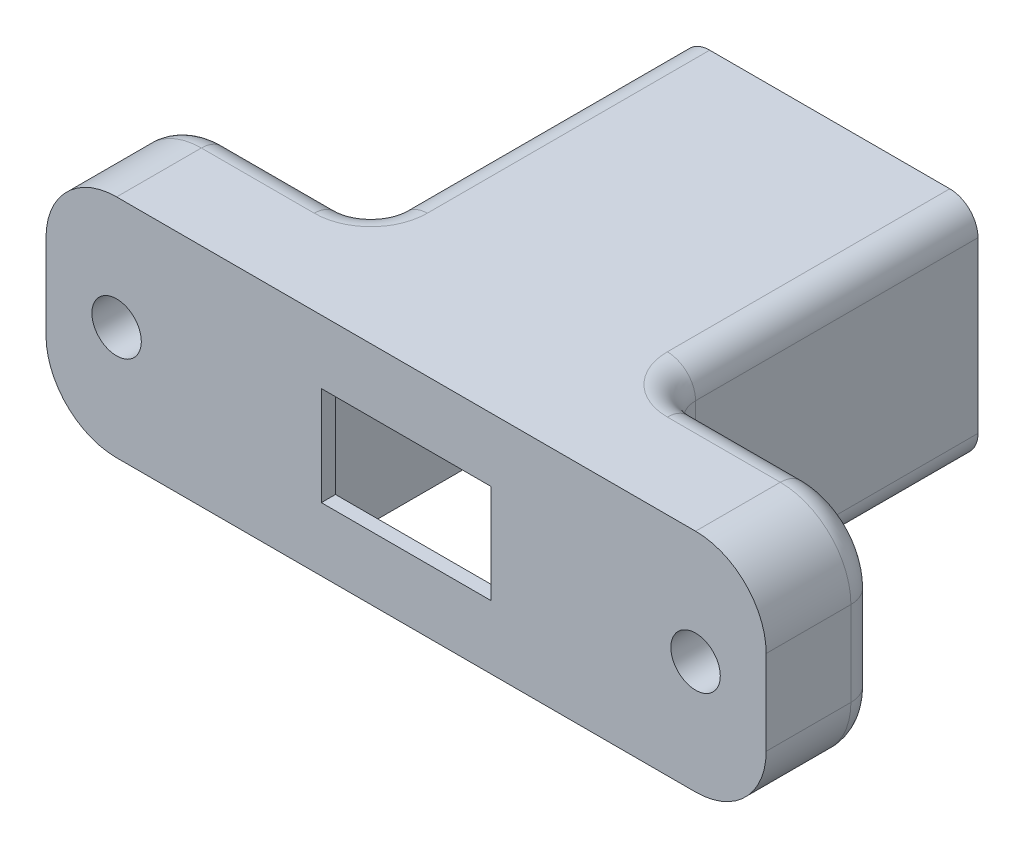
SolidWorks part; units mm, degrees
ref_plane "Front Plane" through (0, 0, 0) normal (0, 0, 1) x (1, 0, 0)
ref_plane "Top Plane" through (0, 0, 0) normal (0, 1, 0) x (1, 0, 0)
ref_plane "Right Plane" through (0, 0, 0) normal (1, 0, 0) x (0, 0, -1)
sketch "Sketch1" plane through (0, 0, 0) normal (0, 0, 1) x (1, 0, 0)
  line L1 (0, 0) -> (15, 0)
  line L2 (0, 0) -> (0, 10)
  line L3 (0, 10) -> (15, 10)
  line L4 (15, 0) -> (15, 10)
  line L5 (-3, 13) -> (18, 13)
  line L6 (-3, 13) -> (-3, -3)
  line L7 (-3, -3) -> (18, -3)
  line L8 (18, 13) -> (18, -3)
  line L9 (1.5, 8.5) -> (13.5, 8.5)
  line L10 (1.5, 8.5) -> (1.5, 1.5)
  line L11 (1.5, 1.5) -> (13.5, 1.5)
  line L12 (13.5, 8.5) -> (13.5, 1.5)
  line L13 (-13, 13) -> (28, 13)
  line L14 (-18, 8) -> (-18, 2)
  line L15 (-13, -3) -> (28, -3)
  line L16 (33, 8) -> (33, 2)
  line L17 (0, 0) -> (15, 0)
  line L18 (0, 0) -> (0, -3)
  line L19 (0, -3) -> (15, -3)
  line L20 (15, 0) -> (15, -3)
  line L21 (-9.7668, 5) -> (-11.3834, 7.8)
  line L22 (-11.3834, 7.8) -> (-14.6166, 7.8)
  line L23 (-14.6166, 7.8) -> (-16.2332, 5)
  line L24 (-16.2332, 5) -> (-14.6166, 2.2)
  line L25 (-14.6166, 2.2) -> (-11.3834, 2.2)
  line L26 (-11.3834, 2.2) -> (-9.7668, 5)
  line L27 (24.7668, 5) -> (26.3834, 2.2)
  line L28 (26.3834, 2.2) -> (29.6166, 2.2)
  line L29 (29.6166, 2.2) -> (31.2332, 5)
  line L30 (31.2332, 5) -> (29.6166, 7.8)
  line L31 (29.6166, 7.8) -> (26.3834, 7.8)
  line L32 (26.3834, 7.8) -> (24.7668, 5)
  circle A0 centre (-13, 5) radius 1.75
  circle A1 centre (28, 5) radius 1.75
  arc A2 (28, -3) -> (33, 2) centre (28, 2) ccw
  arc A3 (28, 13) -> (33, 8) centre (28, 8) cw
  arc A4 (-18, 2) -> (-13, -3) centre (-13, 2) ccw
  arc A5 (-13, 13) -> (-18, 8) centre (-13, 8) ccw
  circle A6 centre (-13, 5) radius 2.8 construction
  circle A7 centre (28, 5) radius 2.8 construction
  point P9 (7.5, 10)
  point P10 (7.5, 13)
  point P11 (-3, 5)
  point P12 (0, 5)
  point P17 (7.5, 8.5)
  point P18 (1.5, 5)
  point P23 (7.5, 0)
  point P28 (7.5, -3)
  dimension "D6" = 3.5
  dimension "D11" = 5
  dimension "D12" = 5.6
  dimension "D1" = 15
  dimension "D2" = 10
  dimension "D3" = 3
  dimension "3" = 3
  dimension "D4" = 1.5
  dimension "D5" = 1.5
  dimension "D7" = 5
  dimension "D8" = 5
  dimension "D9" = 10
  dimension "D10" = 41
extrude "Boss-Extrude1" add sketch "Sketch1" along normal blind 1 contours L1 L4 L3 L2 L9 L12 L11 L10 | L20 L1 L18 L15 | L4 L20 L7 L8 L5 L6 L18 L2 L3 | L13 A5 L14 A4 L15 L6 L26 L25 L24 L23 L22 L21 | L25 L26 L21 L22 L23 L24 A0 | A3 L13 L8 L15 A2 L16 L32 L31 L30 L29 L28 L27 | L31 L32 L27 L28 L29 L30 A1 region at (0.1803, 5, 0) region at (-0.264, -1.5, 0) region at (7.5, -1.5, 0) region at (-8, -2.7807, 0) region at (18.2193, 5, 0) region at (-10.6492, 3.6428, 0) region at (25.6492, 6.3572, 0)
extrude "Boss-Extrude2" add sketch "Sketch1<4>" against normal blind 24 contours L4 L20 L7 L8 L5 L6 L18 L2 L3 region at (-0.264, -1.5, 0)
sketch "Sketch1<4>" plane through (0, 0, 0) normal (0, 0, 1) x (1, 0, 0) same geometry as "Sketch1"
extrude "Boss-Extrude3" add sketch "Sketch1<5>" against normal blind 7 contours A3 L13 L8 L15 A2 L16 L32 L31 L30 L29 L28 L27 | L31 L32 L27 L28 L29 L30 A1 | L13 A5 L14 A4 L15 L6 L26 L25 L24 L23 L22 L21 | L25 L26 L21 L22 L23 L24 A0 region at (-8, -2.7807, 0) region at (18.2193, 5, 0) region at (-10.6492, 3.6428, 0) region at (25.6492, 6.3572, 0)
sketch "Sketch1<5>" plane through (0, 0, 0) normal (0, 0, 1) x (1, 0, 0) same geometry as "Sketch1"
sketch "Sketch2" plane through (0, 0, -24) normal (0, 0, -1) x (-1, 0, 0)
  line L0 (-13.5, 8.5) -> (-13.5, 1.5) construction
  line L1 (-1.5, 8.5) -> (-13.5, 8.5) construction
  line L2 (0, -3) -> (-5.9353, 10)
  line L3 (9.7668, 5) -> (11.3834, 2.2)
  line L4 (11.3834, 2.2) -> (14.6166, 2.2)
  line L5 (14.6166, 2.2) -> (16.2332, 5)
  line L6 (16.2332, 5) -> (14.6166, 7.8)
  line L7 (14.6166, 7.8) -> (11.3834, 7.8)
  line L8 (11.3834, 7.8) -> (9.7668, 5)
  line L9 (-24.7668, 5) -> (-26.3834, 7.8)
  line L10 (-26.3834, 7.8) -> (-29.6166, 7.8)
  line L11 (-29.6166, 7.8) -> (-31.2332, 5)
  line L12 (-31.2332, 5) -> (-29.6166, 2.2)
  line L13 (-29.6166, 2.2) -> (-26.3834, 2.2)
  line L14 (-26.3834, 2.2) -> (-24.7668, 5)
  line L15 (3, -3) -> (-18, -3)
  line L16 (3, -3) -> (3, 13)
  line L17 (3, 13) -> (-18, 13)
  line L18 (-18, -3) -> (-18, 13)
  line L20 (0, 10) -> (-15, 10) construction
  line L21 (-15, -3) -> (-9.0647, 10)
  line L22 (-9.0647, 10) -> (-5.9353, 10)
  circle A0 centre (-7.5, 5) radius 3.5
  circle A1 centre (13, 5) radius 2.8 construction
  circle A2 centre (-28, 5) radius 2.8 construction
  point P5 (-13.5, 5)
  point P10 (-7.5, 8.5)
  line M6 (-15, -3) -> (-15, 10)
  line M7 (-15, 10) -> (0, 10)
  line M8 (0, 10) -> (0, -3)
  line M9 (0, -3) -> (3, -3)
  line M10 (3, -3) -> (3, 13)
  line M11 (3, 13) -> (-18, 13)
  line M12 (-18, 13) -> (-18, -3)
  line M13 (-18, -3) -> (-15, -3)
  dimension "D1" = 7
extrude "Boss-Extrude4" add sketch "Sketch2" along normal blind 5 contours M13 M6 M7 M8 M9 M10 M11 M12 | L2 M8 M7 | L21 M6 M7 region at (-0.264, 3.5, -24) region at (1.9784, 5.6667, -24) region at (13.0216, 5.6667, -24)
extrude "Cut-Extrude1" cut sketch "Sketch2<4>" against normal offset from surface (20 mm away) 3 contours L7 L8 L3 L4 L5 L6 | L13 L14 L9 L10 L11 L12 region at (-13, 5, -24) region at (28, 5, -24) up to face at (-11.6785, 5, -7) offset beyond the face yes
sketch "Sketch2<4>" plane through (0, 0, -24) normal (0, 0, -1) x (-1, 0, 0) same geometry as "Sketch2"
fillet "Fillet1" radius 2 16 edges at (18, 13, -18) (18, -3, -18) (-3, 13, -18) (-3, -3, -18) (23, 13, -7) (23, -3, -7) (31.5355, -1.5355, -7) (33, 5, -7) (-8, 13, -7) (-8, -3, -7) (-16.5355, -1.5355, -7) (-18, 5, -7) (18, 5, -7) (31.5355, 11.5355, -7) (-3, 5, -7) (-16.5355, 11.5355, -7)
